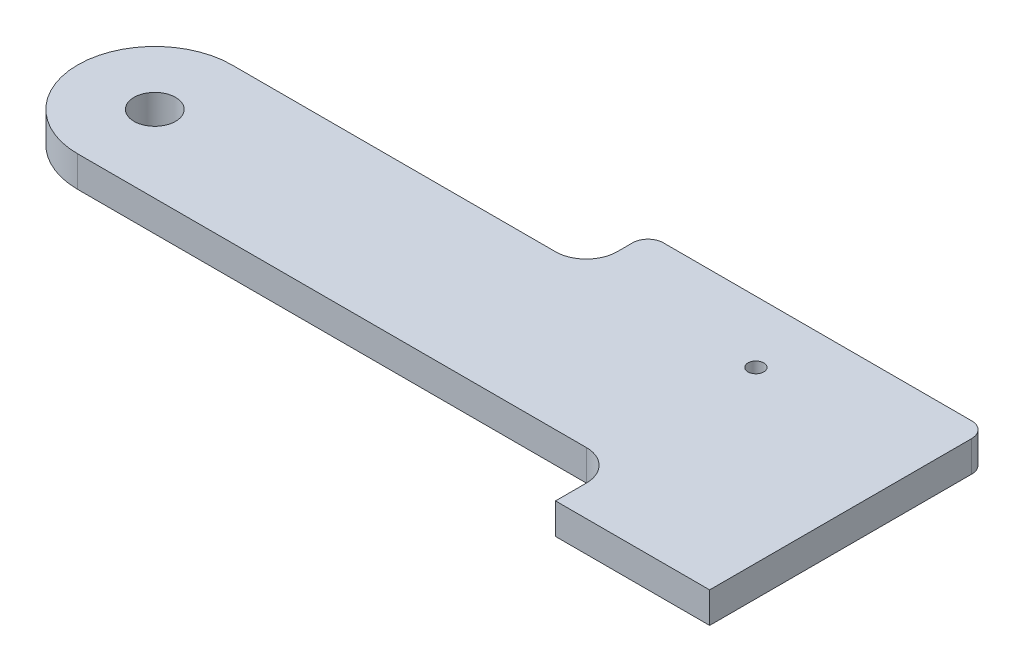
SolidWorks part; units mm, degrees
ref_plane "Front Plane" through (0, 0, 0) normal (0, 0, 1) x (1, 0, 0)
ref_plane "Top Plane" through (0, 0, 0) normal (0, 1, 0) x (1, 0, 0)
ref_plane "Right Plane" through (0, 0, 0) normal (1, 0, 0) x (0, 0, -1)
sketch "Sketch1" plane through (0, 0, 0) normal (0, 1, 0) x (1, 0, 0)
  line L1 (-125, -25) -> (125, -25)
  line L2 (-125, -25) -> (-125, 25)
  line L3 (-125, 25) -> (125, 25)
  line L4 (125, -25) -> (125, 25)
  line L5 (-125, -25) -> (125, 25) construction
  line L6 (-125, 25) -> (125, -25) construction
  point P0 (0, 0)
  dimension "D1" = 250
  dimension "D2" = 50
extrude "Boss-Extrude1" add sketch "Sketch1" along normal blind 10
fillet "Fillet2" radius 25 2 edges at (-125, 5, 25) (-125, 5, -25)
sketch "Sketch4" plane through (0, 10, 0) normal (0, 1, 0) x (1, 0, 0)
  circle A0 centre (-100, 0) radius 6.75
  dimension "D1" = 13.5
extrude "Cut-Extrude3" cut sketch "Sketch4" against normal through all
sketch "Sketch5" plane through (0, 0, -25) normal (0, 0, -1) x (-1, 0, 0)
  line L0 (-125, 10) -> (100, 10) construction
  line L1 (-125, 0) -> (-15, 0)
  line L2 (-125, 0) -> (-125, 10)
  line L3 (-125, 10) -> (-15, 10)
  line L4 (-15, 0) -> (-15, 10)
  dimension "D1" = 110
extrude "Boss-Extrude2" add sketch "Sketch5" along normal blind 20
sketch "Sketch6" plane through (0, 0, 25) normal (0, 0, 1) x (1, 0, 0)
  line L0 (-100, 10) -> (125, 10) construction
  line L1 (125, 0) -> (75, 0)
  line L2 (125, 0) -> (125, 10)
  line L3 (125, 10) -> (75, 10)
  line L4 (75, 0) -> (75, 10)
  dimension "D1" = 50
extrude "Boss-Extrude3" add sketch "Sketch6" along normal blind 20
fillet "Fillet3" radius 10 2 edges at (75, 5, 25) (15, 5, -25)
fillet "Fillet4" radius 5 2 edges at (125, 5, -45) (15, 5, -45)
sketch "Sketch7" plane through (0, 0, 0) normal (0, -1, 0) x (1, 0, 0)
  circle A0 centre (70, -25) radius 2.5527 construction
  circle A1 centre (70, -25) radius 2.5527
extrude "Cut-Extrude4" cut sketch "Sketch7" against normal through all
